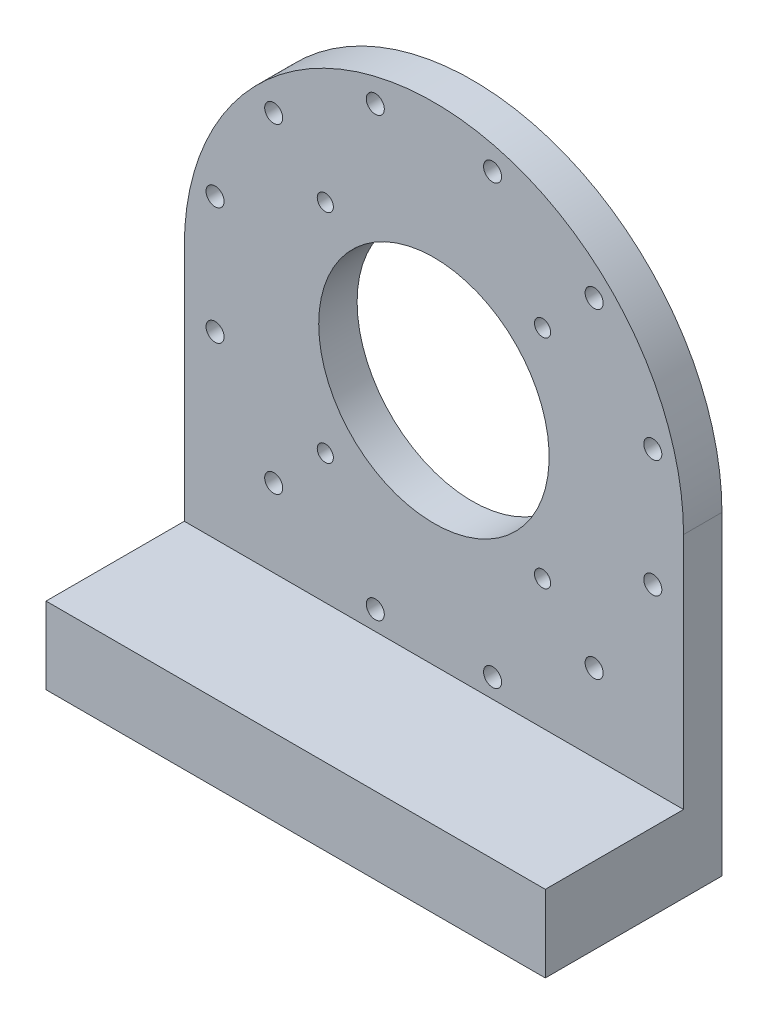
SolidWorks part; units mm, degrees
ref_plane "Front Plane" through (0, 0, 0) normal (0, 0, 1) x (1, 0, 0)
ref_plane "Top Plane" through (0, 0, 0) normal (0, 1, 0) x (1, 0, 0)
ref_plane "Right Plane" through (0, 0, 0) normal (1, 0, 0) x (0, 0, -1)
sketch "Sketch1" plane through (0, 0, -97.5071) normal (0, 0, -1) x (-1, 0, 0)
  line L0 (-154.0728, 47.2587) -> (-154.0728, -14.7413)
  line L1 (-24.0728, 47.2587) -> (-24.0728, -14.7413)
  line L2 (-154.0728, -14.7413) -> (-24.0728, -14.7413)
  line L4 (-154.0728, -14.7413) -> (-24.0728, -14.7413)
  line L5 (-154.0728, -14.7413) -> (-154.0728, -34.7413)
  line L6 (-154.0728, -34.7413) -> (-24.0728, -34.7413)
  line L7 (-24.0728, -14.7413) -> (-24.0728, -34.7413)
  line L9 (-24.0728, -14.7413) -> (-24.0728, -34.7413)
  line L13 (-154.0728, -34.7413) -> (-154.0728, -14.7413)
  arc A0 (-24.0728, 47.2587) -> (-154.0728, 47.2587) centre (-89.0728, 47.2587) ccw
  point P12 (0, 0)
  point P13 (0, 0)
  line M11 (-116.0728, 53.2587) -> (-116.0728, 41.2587)
  line M12 (-116.0728, 41.2587) -> (-149.777, 41.2587)
  arc M13 (-149.777, 41.2587) -> (-149.777, 53.2587) centre (-89.0728, 47.2587) ccw
  line M14 (-149.777, 53.2587) -> (-116.0728, 53.2587)
  circle M15 centre (-117.3571, 18.9744) radius 2.1
  circle M16 centre (-60.7885, 18.9744) radius 2.1
  circle M17 centre (-60.7885, 75.543) radius 2.1
  circle M18 centre (-117.3571, 75.543) radius 2.1
  circle M19 centre (-104.3431, 104.2483) radius 1.575
  circle M20 centre (-146.0624, 62.529) radius 1.575
  circle M21 centre (-130.7921, 5.5394) radius 1.575
  circle M22 centre (-73.8025, -9.7309) radius 1.575
  circle M23 centre (-32.0832, 31.9884) radius 1.575
  circle M24 centre (-32.0832, 62.529) radius 1.575
  circle M25 centre (-47.3535, 88.978) radius 1.575
  circle M26 centre (-47.3535, 5.5394) radius 1.575
  circle M27 centre (-104.3431, -9.7309) radius 1.575
  circle M28 centre (-146.0624, 31.9884) radius 1.575
  circle M29 centre (-130.7921, 88.978) radius 1.575
  circle M30 centre (-73.8025, 104.2483) radius 1.575
  circle M31 centre (-89.0728, 47.2587) radius 15
  dimension "D3" = 65
  dimension "D1" = 20
  dimension "D2" = 62
  dimension "D4" = 130
extrude "Boss-Extrude1" add sketch "Sketch1" along normal blind 10 contours L1 A0 L0 L2 M11 M14 M13 M12 | L7 L2 L5 L6 | M14 M11 M12 M13 M15 M17 M19 M21 M23 M25 M27 M29 M31 M30 M28 M26 M24 M22 M20 M18 M16 region at (89.0728, 110.4413, -97.5071) region at (89.0728, -24.7413, -97.5071) region at (132.9249, 54.982, -97.5071)
extrude "Boss-Extrude2" add sketch "Sketch1<3>" against normal blind 36 contours L7 L2 L5 L6 region at (89.0728, -24.7413, -97.5071)
sketch "Sketch1<3>" plane through (0, 0, -97.5071) normal (0, 0, -1) x (-1, 0, 0) same geometry as "Sketch1"
sketch "Sketch2" plane through (0, 0, -107.5071) normal (0, 0, -1) x (-1, 0, 0)
  circle A0 centre (-89.0728, 47.2587) radius 30
  dimension "D1" = 60
extrude "Cut-Extrude1" cut sketch "Sketch2" against normal blind 36
sketch "Sketch4" plane through (0, 0, -107.5071) normal (0, 0, -1) x (-1, 0, 0)
  circle A0 centre (-73.8025, 104.2483) radius 2.35
  circle A1 centre (-47.3535, 88.978) radius 2.35
  circle A2 centre (-32.0832, 62.529) radius 2.35
  circle A3 centre (-32.0832, 31.9884) radius 2.35
  circle A4 centre (-47.3535, 5.5394) radius 2.35
  circle A5 centre (-73.8025, -9.7309) radius 2.35
  circle A6 centre (-104.3431, -9.7309) radius 2.35
  circle A7 centre (-130.7921, 5.5394) radius 2.35
  circle A8 centre (-146.0624, 31.9884) radius 2.35
  circle A9 centre (-146.0624, 62.529) radius 2.35
  circle A10 centre (-130.7921, 88.978) radius 2.35
  circle A11 centre (-104.3431, 104.2483) radius 2.35
  point P3 (-45.6128, 87.4026)
  point P4 (-89.0728, 47.2587)
  point P28 (-89.0728, 47.2587)
  dimension "D1" = 4.7
  dimension "D2" = 12
extrude "Cut-Extrude2" cut sketch "Sketch4" against normal through all
equation "\"helloi\"= 123"
